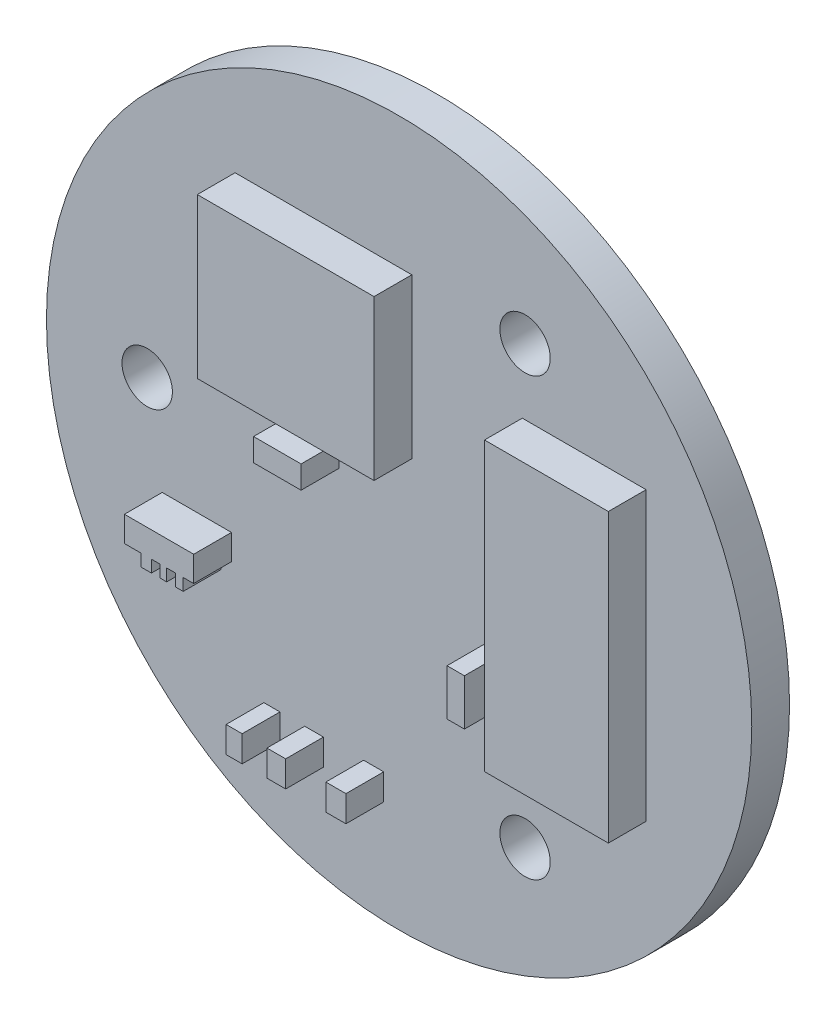
SolidWorks part; units mm, degrees
ref_plane "前视基准面" through (0, 0, 0) normal (0, 0, 1) x (1, 0, 0)
ref_plane "上视基准面" through (0, 0, 0) normal (0, 1, 0) x (1, 0, 0)
ref_plane "右视基准面" through (0, 0, 0) normal (1, 0, 0) x (0, 0, -1)
sketch "草图1" plane through (0, 0, 0) normal (0, 0, 1) x (1, 0, 0)
  circle A0 centre (0, 0) radius 14
extrude "凸台-拉伸1" add sketch "草图1" along normal blind 1.5
sketch "草图2" plane through (0, 0, 0) normal (0, 0, -1) x (-1, 0, 0)
  line L2 (2, 2.5) -> (2, -2.5)
  line L7 (-2, -2.5) -> (-2, 2.5)
  line L8 (2, -2.5) -> (-2, -2.5)
  line L9 (-2, 2.5) -> (2, 2.5)
extrude "凸台-拉伸2" add sketch "草图2" along normal blind 1.8
sketch "草图3" plane through (0, 0, 0) normal (0, 0, -1) x (-1, 0, 0)
  circle A1 centre (10, 0) radius 1
  circle A2 centre (-5, 8.6603) radius 1
  circle A3 centre (-5, -8.6603) radius 1
extrude "切除-拉伸1" cut sketch "草图3" against normal blind 1.8
sketch "草图4" plane through (0, 0, 1.5) normal (0, 0, 1) x (1, 0, 0)
  line L0 (-8.1056, -3.6542) -> (-6.6543, -3.6542)
  line L1 (-6.511, 8.7833) -> (0.5049, 8.7833)
  line L2 (-6.511, 8.7833) -> (-6.511, 2.4582)
  line L3 (-6.511, 2.4582) -> (0.5049, 2.4582)
  line L4 (0.5049, 8.7833) -> (0.5049, 2.4582)
  line L5 (4.8899, 6.046) -> (9.8064, 6.046)
  line L6 (4.8899, 6.046) -> (4.8899, -5.355)
  line L7 (4.8899, -5.355) -> (9.8064, -5.355)
  line L8 (9.8064, 6.046) -> (9.8064, -5.355)
  line L9 (-4.2787, 1.5813) -> (-2.3918, 1.5813)
  line L10 (-4.2787, 1.5813) -> (-4.2787, 0.6777)
  line L11 (-4.2787, 0.6777) -> (-2.3918, 0.6777)
  line L12 (-2.3918, 1.5813) -> (-2.3918, 0.6777)
  line L13 (-5.3683, -8.863) -> (-4.7305, -8.863)
  line L14 (-5.3683, -8.863) -> (-5.3683, -9.8994)
  line L15 (-5.3683, -9.8994) -> (-4.7305, -9.8994)
  line L16 (-4.7305, -8.863) -> (-4.7305, -9.8994)
  line L17 (-3.7472, -8.863) -> (-3.0031, -8.863)
  line L18 (-3.7472, -8.863) -> (-3.7472, -9.8994)
  line L19 (-3.7472, -9.8994) -> (-3.0031, -9.8994)
  line L20 (-3.0031, -8.863) -> (-3.0031, -9.8994)
  line L21 (-1.4085, -8.863) -> (-0.6112, -8.863)
  line L22 (-1.4085, -8.863) -> (-1.4085, -9.8994)
  line L23 (-1.4085, -9.8994) -> (-0.6112, -9.8994)
  line L24 (-0.6112, -8.863) -> (-0.6112, -9.8994)
  line L25 (3.4017, -2.4582) -> (4.0927, -2.4582)
  line L26 (3.4017, -2.4582) -> (3.4017, -4.292)
  line L27 (3.4017, -4.292) -> (4.0927, -4.292)
  line L28 (4.0927, -2.4582) -> (4.0927, -4.292)
  line L29 (-6.6543, -3.6542) -> (-6.6543, -4.6614)
  line L30 (-6.6543, -4.6614) -> (-7.0705, -4.6614)
  line L31 (-7.0705, -4.6614) -> (-7.0705, -5.1407)
  line L32 (-7.0705, -5.1407) -> (-7.3799, -5.1407)
  line L33 (-7.3799, -5.1407) -> (-7.3799, -4.6614)
  line L34 (-7.3799, -4.6614) -> (-7.7264, -4.6614)
  line L35 (-7.7264, -4.6614) -> (-7.7264, -5.1407)
  line L36 (-7.7264, -5.1407) -> (-7.9912, -5.1407)
  line L37 (-7.9912, -5.1407) -> (-7.9912, -4.6614)
  line L38 (-7.9912, -4.6614) -> (-8.3317, -4.6614)
  line L39 (-8.3317, -4.6614) -> (-8.3317, -5.1407)
  line L40 (-8.3317, -5.1407) -> (-8.748, -5.1407)
  line L41 (-8.748, -5.1407) -> (-8.748, -4.6614)
  line L42 (-8.748, -4.6614) -> (-9.4038, -4.6614)
  line L43 (-9.4038, -4.6614) -> (-9.4038, -3.6542)
  line L44 (-9.4038, -3.6542) -> (-8.1056, -3.6542)
extrude "凸台-拉伸3" add sketch "草图4" along normal blind 1.5
